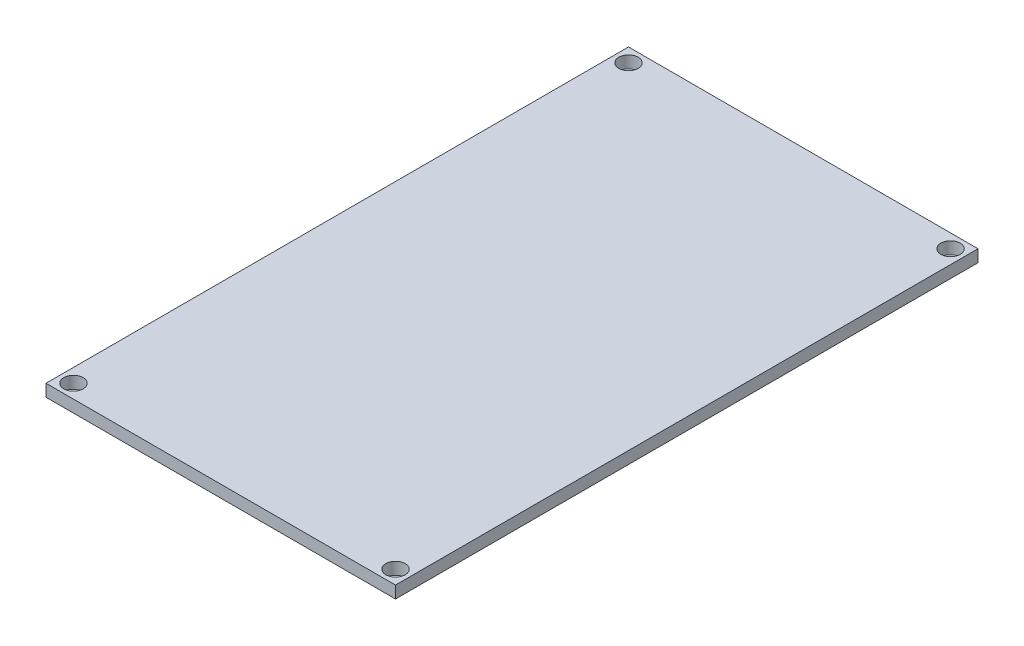
SolidWorks part; units mm, degrees
material "Glass"
ref_plane "Front Plane" through (0, 0, 0) normal (0, 0, 1) x (1, 0, 0)
ref_plane "Top Plane" through (0, 0, 0) normal (0, 1, 0) x (1, 0, 0)
ref_plane "Right Plane" through (0, 0, 0) normal (1, 0, 0) x (0, 0, -1)
sketch "Sketch3" plane through (0, 0, 0) normal (0, 1, 0) x (1, 0, 0)
  line L1 (-18, 26) -> (-18, 35.8093)
  line L2 (-18, 35.8093) -> (-8.1907, 35.8093)
  line L4 (0, 22.5721) -> (0, 0) construction
  line L6 (-17, 5.8093) -> (17, 5.8093) construction
  line L8 (18, 26) -> (18, -14.3815)
  line L9 (-18, 35.8093) -> (-15.1716, 32.9808) construction
  line L11 (-18, 35.8093) -> (-18, 26)
  line L12 (-8.1907, 35.8093) -> (-18, 35.8093)
  line L13 (18, 35.8093) -> (15.1716, 32.9808) construction
  line L14 (8.1907, 35.8093) -> (18, 35.8093)
  line L15 (18, 35.8093) -> (18, 26)
  line L16 (18, 35.8093) -> (8.1907, 35.8093)
  line L17 (18, 26) -> (18, 35.8093)
  line L18 (18, -24.1907) -> (15.1716, -21.3623) construction
  line L19 (-18, -24.1907) -> (-15.1716, -21.3623) construction
  line L20 (18, -14.3815) -> (18, -24.1907)
  line L21 (18, -24.1907) -> (8.1907, -24.1907)
  line L22 (18, -24.1907) -> (18, -14.3815)
  line L23 (8.1907, -24.1907) -> (18, -24.1907)
  line L24 (-8.1907, -24.1907) -> (-18, -24.1907)
  line L25 (-18, -24.1907) -> (-18, -14.3815)
  line L26 (-18, -24.1907) -> (-8.1907, -24.1907)
  line L27 (-18, -14.3815) -> (-18, -24.1907)
  line L31 (8.1907, -24.1907) -> (-8.1907, -24.1907)
  line L32 (-18, -14.3815) -> (-18, 26)
  line L33 (-8.1907, 35.8093) -> (8.1907, 35.8093)
  circle A1 centre (-16.5858, 34.3951) radius 1
  circle A6 centre (16.5858, 34.3951) radius 1
  circle A7 centre (16.5858, -22.7765) radius 1
  circle A10 centre (-16.5858, -22.7765) radius 1
  point P3 (-17, 5.8093)
  point P11 (0, 30)
  dimension "D2" = 2
  dimension "D1" = 1.4142
  dimension "D3" = 30
  dimension "D4" = 18
  dimension "D5" = 35.8093
extrude "Boss-Extrude1" add sketch "Sketch3" along normal blind 1.25 contours L33 L2 L1 L32 L25 L24 L31 L21 L20 L8 L15 L14 A6 A1 A7 A10 region at (0, 0, -5.8093)
